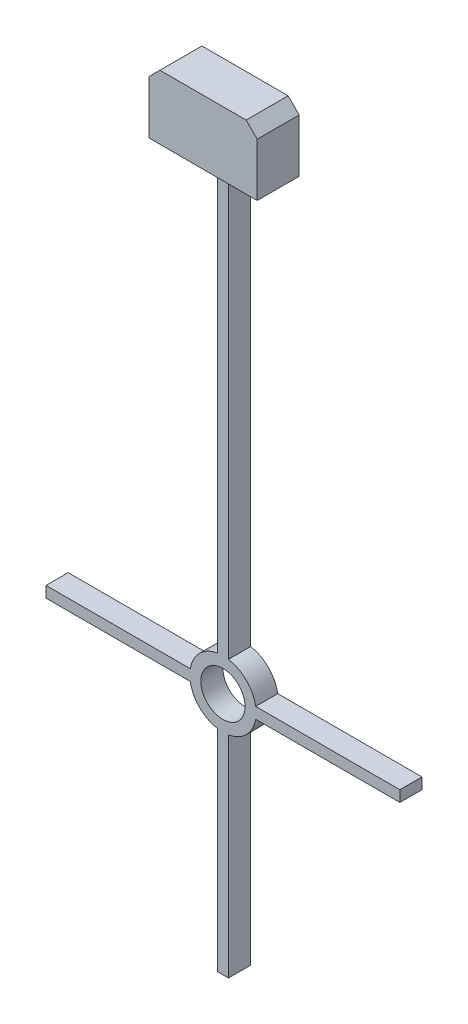
SolidWorks part; units mm, degrees
ref_plane "정면" through (0, 0, 0) normal (0, 0, 1) x (1, 0, 0)
ref_plane "윗면" through (0, 0, 0) normal (0, 1, 0) x (1, 0, 0)
ref_plane "우측면" through (0, 0, 0) normal (1, 0, 0) x (0, 0, -1)
sketch "스케치1" plane through (0, 0, 0) normal (0, 0, 1) x (1, 0, 0)
  line L0 (-1.479, 0.25) -> (-8, 0.25)
  line L1 (-8, 0.25) -> (-8, -0.25)
  line L2 (-8, 0) -> (0, 0) construction
  line L3 (-0.25, 1.479) -> (-0.25, 21)
  line L4 (-0.25, 21) -> (0.25, 21)
  line L5 (0, 21) -> (0, 0) construction
  line L6 (8, 0.25) -> (8, -0.25)
  line L7 (1.479, 0.25) -> (8, 0.25)
  line L8 (0.25, 1.479) -> (0.25, 21)
  line L9 (1.479, -0.25) -> (8, -0.25)
  line L10 (0.25, -1.479) -> (0.25, -21)
  line L11 (-0.25, -21) -> (0.25, -21)
  line L12 (-0.25, -1.479) -> (-0.25, -21)
  line L13 (-1.479, -0.25) -> (-8, -0.25)
  arc A0 (0.25, -1.479) -> (1.479, -0.25) centre (0, 0) ccw
  circle A1 centre (0, 0) radius 1
  arc A2 (-0.25, 1.479) -> (-1.479, 0.25) centre (0, 0) ccw
  arc A3 (0.25, 1.479) -> (1.479, 0.25) centre (0, 0) cw
  arc A4 (-0.25, -1.479) -> (-1.479, -0.25) centre (0, 0) cw
  arc A5 (1.479, 0.25) -> (0.25, 1.479) centre (0, 0) ccw
  point P16 (8, 0)
  dimension "D3" = 2
  dimension "D4" = 1.5
  dimension "D1" = 0.5
  dimension "D2" = 0.5
  dimension "D5" = 21
  dimension "D6" = 8
extrude "보스-돌출1" add sketch "스케치1" along normal mid plane 1 contours A4 L12 L11 L10 A0 L9 L6 L7 A3 L8 L4 L3 A2 L0 L1 L13 A1 region at (-0.7429, 0.7429, 0)
sketch "스케치2" plane through (0, 0, 0) normal (0, 0, 1) x (1, 0, 0)
  line L0 (0, 22.45) -> (0, 0) construction
  line L1 (-2.45, 23.9) -> (2.45, 23.9)
  line L2 (-2.45, 23.9) -> (-2.45, 21)
  line L3 (-2.45, 21) -> (2.45, 21)
  line L4 (2.45, 23.9) -> (2.45, 21)
  line L5 (-2.45, 23.9) -> (2.45, 21) construction
  line L6 (-2.45, 21) -> (2.45, 23.9) construction
  line L7 (-0.25, 21) -> (0.25, 21) construction
  point P0 (0, 22.45)
  dimension "D1" = 2.9
  dimension "D2" = 4.9
extrude "보스-돌출2" add sketch "스케치2" along normal blind 1.4
extrude "보스-돌출3" add sketch "스케치2<2>" against normal up to surface (0.5 mm away) up to face at (0, 0, -0.5)
sketch "스케치2<2>" plane through (0, 0, 0) normal (0, 0, 1) x (1, 0, 0) same geometry as "스케치2"
chamfer "모따기1" distance 0.5 angle 45 2 edges at (2.45, 23.9, 0.45) (-2.45, 23.9, 0.45)
chamfer "모따기2" distance 0.5 angle 45 2 edges at (0.25, 21, 0) (-0.25, 21, 0)
sketch "스케치3" plane through (0, 0, 0) normal (0, 0, 1) x (1, 0, 0)
  line L0 (-0.25, -21) -> (0.25, -21) construction
  line L1 (-5.8096, -31) -> (5.8096, -31)
  line L2 (-5.8096, -31) -> (-5.8096, -11)
  line L3 (-5.8096, -11) -> (5.8096, -11)
  line L4 (5.8096, -31) -> (5.8096, -11)
  line L5 (-5.8096, -31) -> (5.8096, -11) construction
  line L6 (-5.8096, -11) -> (5.8096, -31) construction
  point P0 (0, -21)
  dimension "D1" = 10
extrude "컷-돌출1" cut sketch "스케치3" against normal mid plane 10
